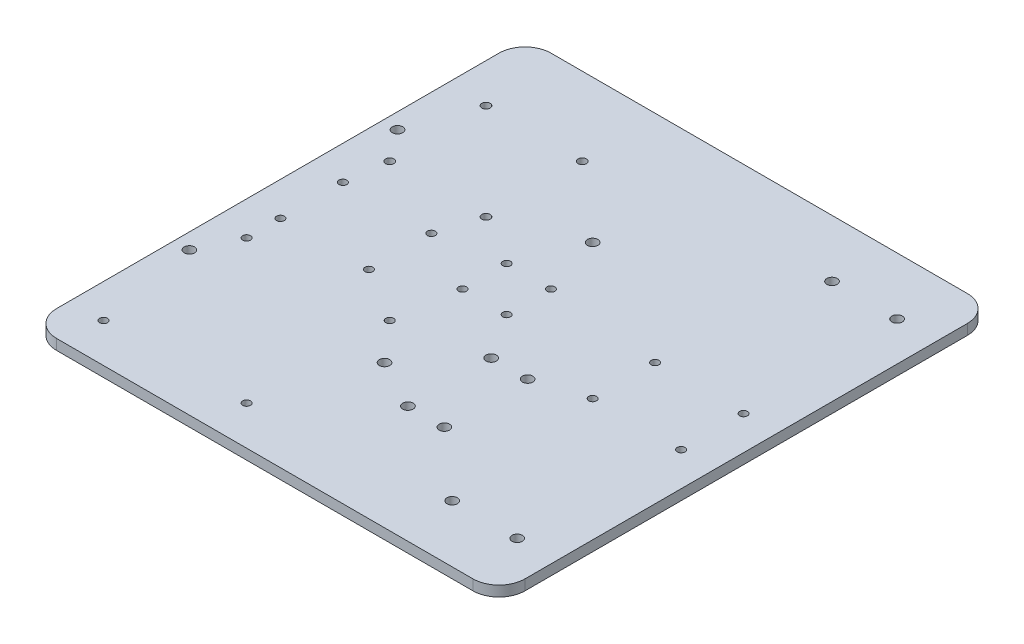
SolidWorks part; units mm, degrees
ref_plane "前视基准面" through (0, 0, 0) normal (0, 0, 1) x (1, 0, 0)
ref_plane "上视基准面" through (0, 0, 0) normal (0, 1, 0) x (1, 0, 0)
ref_plane "右视基准面" through (0, 0, 0) normal (1, 0, 0) x (0, 0, -1)
other "Configuration Table"
sketch "草图1" plane through (0, 0, 0) normal (0, 1, 0) x (1, 0, 0)
  line L1 (-90, -95) -> (90, -95)
  line L2 (-90, -95) -> (-90, 95)
  line L3 (-90, 95) -> (90, 95)
  line L4 (90, -95) -> (90, 95)
  line L5 (-90, -95) -> (90, 95) construction
  line L6 (-90, 95) -> (90, -95) construction
  point P0 (0, 0)
  dimension "D1" = 190
  dimension "D2" = 180
extrude "凸台-拉伸1" add sketch "草图1" along normal blind 4
sketch "草图2" plane through (0, 4, 0) normal (0, 1, 0) x (1, 0, 0)
  line L0 (90, -95) -> (90, 95) construction
  line L1 (66, -25) -> (85, -25) construction
  line L2 (66, -25) -> (66, 25) construction
  line L3 (66, 25) -> (85, 25) construction
  line L4 (85, -25) -> (85, 25) construction
  line L5 (66, -25) -> (85, 25) construction
  line L6 (66, 25) -> (85, -25) construction
  circle A0 centre (66, 25) radius 1.6
  circle A1 centre (66, -25) radius 1.6
  circle A2 centre (85, -25) radius 1.6
  circle A3 centre (85, 25) radius 1.6
  circle A7 centre (80.7, 7) radius 3
  point P0 (75.5, 0)
  dimension "D4" = 3.2
  dimension "D5" = 4.3
  dimension "D7" = 6
  dimension "D1" = 19
  dimension "D2" = 50
  dimension "D3" = 5
  dimension "D6" = 18
sketch "草图4" plane through (0, 4, 0) normal (0, 1, 0) x (1, 0, 0)
  line L0 (90, 95) -> (-90, 95) construction
  line L1 (-75, 65) -> (-38, 65) construction
  line L2 (-75, 65) -> (-75, 28) construction
  line L3 (-75, 28) -> (-38, 28) construction
  line L4 (-38, 65) -> (-38, 28) construction
  line L5 (-90, 95) -> (-90, -95) construction
  circle A0 centre (-75, 65) radius 1.6
  circle A1 centre (-38, 65) radius 1.6
  circle A2 centre (-38, 28) radius 1.6
  circle A3 centre (-75, 28) radius 1.6
  dimension "D4" = 3.2
  dimension "D1" = 37
  dimension "D2" = 30
  dimension "D3" = 15
extrude "切除-拉伸3" cut sketch "草图4" against normal blind 4
sketch "草图5" plane through (0, 4, 0) normal (0, 1, 0) x (1, 0, 0)
  line L5 (-90, 95) -> (-90, -95) construction
  line L7 (-22, -80) -> (-77, -80) construction
  line L8 (-22, -80) -> (-22, -25) construction
  line L9 (-22, -25) -> (-77, -25) construction
  line L10 (-77, -80) -> (-77, -25) construction
  line L11 (-90, -95) -> (90, -95) construction
  circle A8 centre (-77, -80) radius 1.5
  circle A9 centre (-77, -25) radius 1.5
  circle A10 centre (-22, -25) radius 1.5
  circle A11 centre (-22, -80) radius 1.5
  dimension "D2" = 3
  dimension "D1" = 55
  dimension "D3" = 13
  dimension "D4" = 15
extrude "切除-拉伸4" cut sketch "草图5" against normal blind 4
sketch "草图7" plane through (0, 0, 0) normal (0, -1, 0) x (1, 0, 0)
  line L0 (-90, 95) -> (90, 95) construction
  line L2 (90, 95) -> (90, -95) construction
  circle A0 centre (24, 50) radius 2
  circle A1 centre (10, 50) radius 2
  circle A2 centre (24, 18) radius 2
  circle A3 centre (10, 18) radius 2
  dimension "D2" = 4
  dimension "D5" = 4
  dimension "D1" = 80
  dimension "D3" = 45
  dimension "D6" = 14
  dimension "D7" = 32
extrude "切除-拉伸5" cut sketch "草图7" against normal blind 10
sketch "草图8" plane through (0, 0, 0) normal (0, -1, 0) x (1, 0, 0)
  line L1 (-18.5, -16.45) -> (-1.5, -16.45) construction
  line L2 (-18.5, -16.45) -> (-18.5, 0.55) construction
  line L3 (-18.5, 0.55) -> (-1.5, 0.55) construction
  line L4 (-1.5, -16.45) -> (-1.5, 0.55) construction
  line L5 (-18.5, -16.45) -> (-1.5, 0.55) construction
  line L6 (-18.5, 0.55) -> (-1.5, -16.45) construction
  circle A0 centre (-18.5, 0.55) radius 1.5
  circle A1 centre (-1.5, 0.55) radius 1.5
  circle A2 centre (-18.5, -16.45) radius 1.5
  circle A3 centre (-1.5, -16.45) radius 1.5
  point P0 (-10, -7.95)
  point P10 (-10, -4.8636)
  dimension "D4" = 3
  dimension "D1" = 17
  dimension "D2" = 7.95
  dimension "D3" = 10
extrude "切除-拉伸6" cut sketch "草图8" against normal blind 10
sketch "草图11" plane through (0, 0, 0) normal (0, -1, 0) x (1, 0, 0)
  line L0 (60, 95) -> (60, -95) construction
  line L1 (-90, 0) -> (90, 0) construction
  line L2 (90, 95) -> (90, -95) construction
  line L3 (-90, -95) -> (-90, 95) construction
  line L4 (90, -95) -> (-90, -95) construction
  line L5 (-90, 95) -> (90, 95) construction
  circle A0 centre (77, 12) radius 1.5
  circle A1 centre (43, 12) radius 1.5
  circle A2 centre (77, -12) radius 1.5
  circle A3 centre (43, -12) radius 1.5
  dimension "D1" = 3
  dimension "D2" = 24
  dimension "D3" = 34
  dimension "D4" = 30
extrude "切除-拉伸8" cut sketch "草图11" against normal blind 4
sketch "草图12" plane through (0, 0, 0) normal (0, -1, 0) x (1, 0, 0)
  line L0 (-90, -95) -> (-90, 95) construction
  line L1 (-9, -40) -> (-84, -40) construction
  line L2 (-9, -40) -> (-9, 40) construction
  line L3 (-9, 40) -> (-84, 40) construction
  line L4 (-84, -40) -> (-84, 40) construction
  line L5 (-9, -40) -> (-84, 40) construction
  line L6 (-9, 40) -> (-84, -40) construction
  circle A0 centre (-84, 40) radius 2
  circle A1 centre (-9, 40) radius 2
  circle A2 centre (-9, -40) radius 2
  circle A3 centre (-84, -40) radius 2
  point P0 (-46.5, 0)
  dimension "D4" = 4
  dimension "D1" = 6
  dimension "D2" = 75
  dimension "D3" = 80
extrude "切除-拉伸9" cut sketch "草图12" against normal blind 4
sketch "草图15" plane through (0, 4, 0) normal (0, 1, 0) x (1, 0, 0)
  line L1 (90, -95) -> (90, 95) construction
  line L2 (0, 0) -> (50000, 0) construction
  circle A0 centre (75, -73) radius 2
  circle A1 centre (50, -73) radius 2
  dimension "D2" = 4
  dimension "D5" = 4
  dimension "D1" = 73
  dimension "D3" = 15
  dimension "D4" = 25
extrude "切除-拉伸10" cut sketch "草图15" against normal through all
mirror "镜向2" about plane through (0, 0, 0) normal (0, 0, 1) of "切除-拉伸10"
fillet "圆角2" radius 10 4 edges at (-90, 2, 95) (90, 2, 95) (90, 2, -95) (-90, 2, -95)
mirror "镜向3" about plane through (0, 0, 0) normal (1, 0, 0) of "切除-拉伸8"
